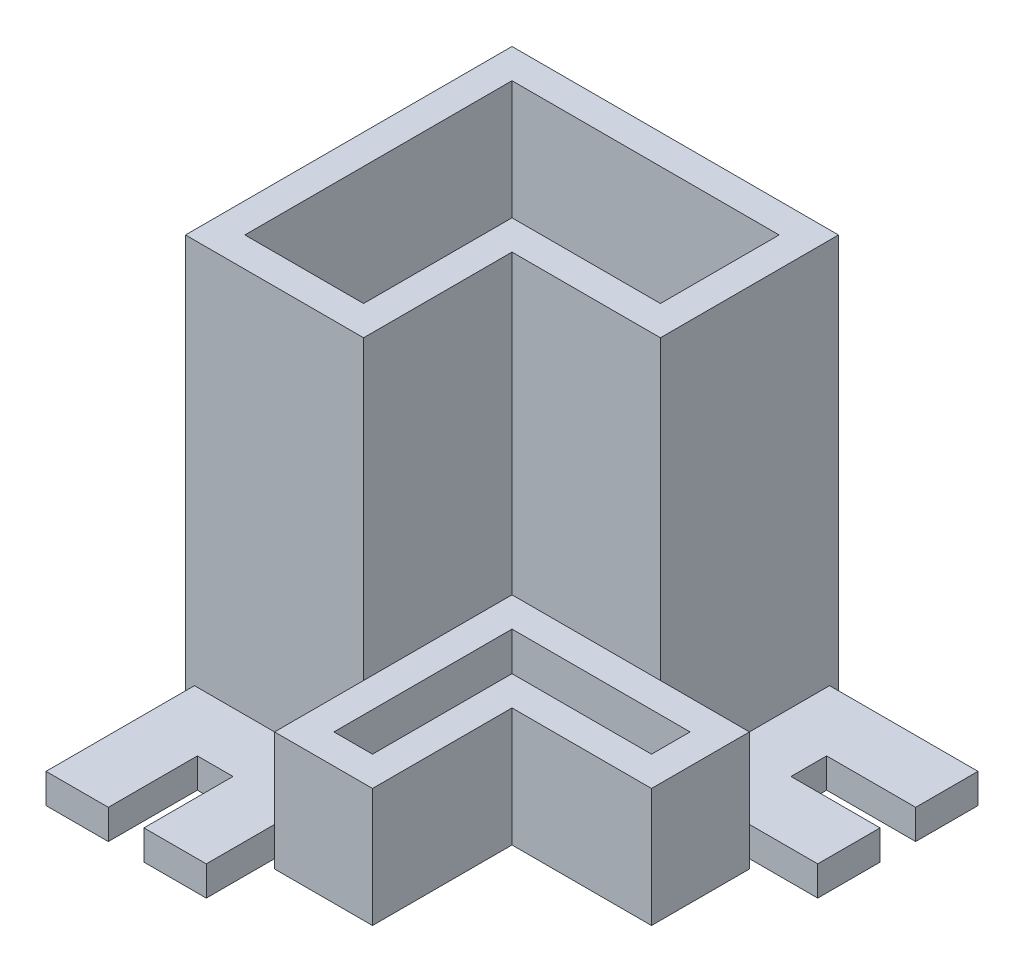
SolidWorks part; units mm, degrees
ref_plane "Ön Düzlem" through (0, 0, 0) normal (0, 0, 1) x (1, 0, 0)
ref_plane "Üst Düzlem" through (0, 0, 0) normal (0, 1, 0) x (1, 0, 0)
ref_plane "Sağ Düzlem" through (0, 0, 0) normal (1, 0, 0) x (0, 0, -1)
sketch "Sketch1" plane through (0, 0, 0) normal (0, 1, 0) x (1, 0, 0)
  line L0 (0, 0) -> (23.5, 0)
  line L1 (23.5, 0) -> (0, 0)
  line L2 (0, -23.5) -> (0, 0)
  line L3 (23.5, 0) -> (23.5, 16.5)
  line L4 (23.5, 16.5) -> (-16.5, 16.5)
  line L5 (-16.5, 16.5) -> (-16.5, -23.5)
  line L6 (-16.5, -23.5) -> (0, -23.5)
  line L7 (23.5, 16.5) -> (8.5, 16.5)
  line L8 (8.5, 16.5) -> (8.5, 46.5)
  line L9 (8.5, 46.5) -> (-46.5, 46.5)
  line L10 (-46.5, 46.5) -> (-46.5, -8.5)
  line L11 (-46.5, -8.5) -> (-16.5, -8.5)
  line L12 (-16.5, -8.5) -> (-16.5, -23.5)
  line L13 (8.5, 45) -> (33.5, 45)
  line L14 (33.5, 45) -> (33.5, 34.5)
  line L15 (33.5, 34.5) -> (18.5, 34.5)
  line L16 (18.5, 34.5) -> (18.5, 28.5)
  line L17 (18.5, 28.5) -> (33.5, 28.5)
  line L18 (33.5, 28.5) -> (33.5, 18)
  line L19 (33.5, 18) -> (8.5, 18)
  line L20 (-45, -8.5) -> (-45, -33.5)
  line L21 (-45, -33.5) -> (-34.5, -33.5)
  line L22 (-34.5, -33.5) -> (-34.5, -18.5)
  line L23 (-34.5, -18.5) -> (-28.5, -18.5)
  line L24 (-28.5, -18.5) -> (-28.5, -33.5)
  line L25 (-28.5, -33.5) -> (-18, -33.5)
  line L26 (-18, -33.5) -> (-18, -8.5)
  dimension "D1" = 16.5
  dimension "D2" = 55
  dimension "D3" = 30
  dimension "D4" = 6
  dimension "D5" = 27
  dimension "D6" = 1.5
  dimension "D7" = 10
  dimension "D8" = 25
  dimension "D9" = 1.5
  dimension "D10" = 6
  dimension "D11" = 27
  dimension "D12" = 10
  dimension "D13" = 25
  dimension "D14" = 40
extrude "Boss-Extrude1" add sketch "Sketch1" along normal blind 70 contours L11 L12 L5 L4 L7 L8 L9 L10 region at (-22.9063, 0, -22.9062)
extrude "Boss-Extrude2" add sketch "Sketch1<3>" along normal blind 20 contours L5 L6 L2 L0 L3 L4 region at (-0.8484, 0, -0.8484)
sketch "Sketch1<3>" plane through (0, 0, 0) normal (0, 1, 0) x (1, 0, 0) same geometry as "Sketch1"
extrude "Boss-Extrude3" add sketch "Sketch1<4>" along normal blind 5 contours L19 L18 L17 L16 L15 L14 L13 L8 | L25 L26 L11 L20 L21 L22 L23 L24 region at (8.868, 0, -31.5) region at (-18.368, 0, 21)
sketch "Sketch1<4>" plane through (0, 0, 0) normal (0, 1, 0) x (1, 0, 0) same geometry as "Sketch1"
sketch "Sketch2" plane through (0, 70, 0) normal (0, 1, 0) x (1, 0, 0)
  line L0 (-41.5, 41.5) -> (3.5, 41.5)
  line L1 (3.5, 41.5) -> (3.5, 21.5)
  line L3 (-21.5, 21.5) -> (-21.5, -3.5)
  line L4 (-21.5, -3.5) -> (-41.5, -3.5)
  line L5 (-41.5, -3.5) -> (-41.5, 41.5)
  line L6 (-46.5, 46.5) -> (-46.5, -8.5) construction
  line L7 (8.5, 46.5) -> (-46.5, 46.5) construction
  line L8 (8.5, 18) -> (8.5, 45) construction
  line L10 (-16.5, -8.5) -> (-16.5, 16.5) construction
  line L11 (-46.5, -8.5) -> (-16.5, -8.5) construction
  line L12 (-21.5, 21.5) -> (3.5, 21.5)
  line L13 (8.5, 16.5) -> (-16.5, 16.5) construction
  dimension "D1" = 5
  dimension "D2" = 5
  dimension "D3" = 5
  dimension "D4" = 5
  dimension "D5" = 5
  dimension "D6" = 5
extrude "Cut-Extrude1" cut sketch "Sketch2" against normal up to surface (70 mm away) up to face at (-4.8462, 0, -4.8462)
sketch "Sketch3" plane through (0, 20, 0) normal (0, 1, 0) x (1, 0, 0)
  line L0 (18.5, 5) -> (18.5, 11.5)
  line L1 (18.5, 11.5) -> (-11.5, 11.5)
  line L2 (-11.5, 11.5) -> (-11.5, -18.5)
  line L3 (-11.5, -18.5) -> (-5, -18.5)
  line L4 (-5, -18.5) -> (-5, 5)
  line L5 (-5, 5) -> (18.5, 5)
  line L6 (23.5, 16.5) -> (8.5, 16.5) construction
  line L7 (23.5, 0) -> (23.5, 16.5) construction
  line L8 (0, 0) -> (23.5, 0) construction
  line L9 (0, -23.5) -> (0, 0) construction
  line L10 (-16.5, -23.5) -> (0, -23.5) construction
  line L11 (-16.5, 16.5) -> (-16.5, -8.5) construction
  dimension "D1" = 5
  dimension "D2" = 5
  dimension "D3" = 5
  dimension "D4" = 5
  dimension "D5" = 5
  dimension "D6" = 5
extrude "Cut-Extrude2" cut sketch "Sketch3" against normal up to surface (20 mm away) up to face at (-19.8333, 0, -19.8333)
